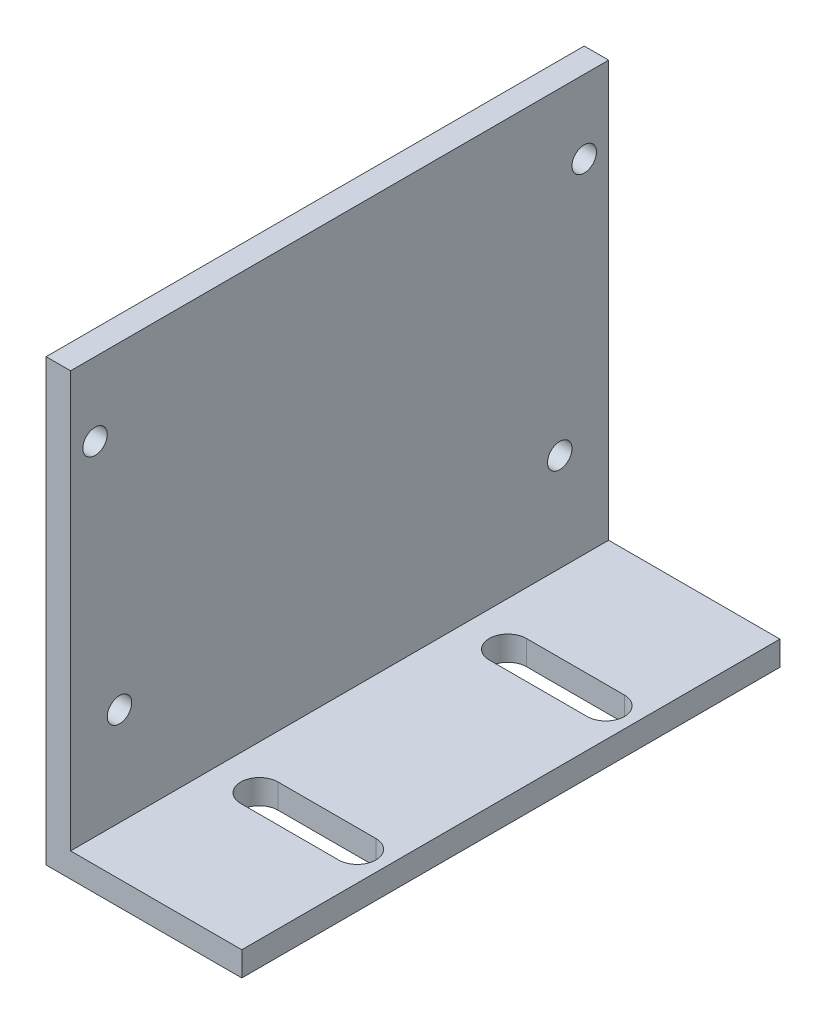
SolidWorks part; units mm, degrees
ref_plane "Front Plane" through (0, 0, 0) normal (0, 0, 1) x (1, 0, 0)
ref_plane "Top Plane" through (0, 0, 0) normal (0, 1, 0) x (1, 0, 0)
ref_plane "Right Plane" through (0, 0, 0) normal (1, 0, 0) x (0, 0, -1)
sketch "Sketch1" plane through (0, 0, 0) normal (0, 0, 1) x (1, 0, 0)
  line L0 (0, 0) -> (-20, 0)
  line L1 (-20, 0) -> (-20, 45)
  line L2 (-20, 45) -> (-17.5, 45)
  line L3 (-17.5, 45) -> (-17.5, 2.5)
  line L4 (-17.5, 2.5) -> (0, 2.5)
  line L5 (0, 2.5) -> (0, 0)
  point P7 (0, -0.2069)
  dimension "D1" = 45
  dimension "D2" = 20
  dimension "D3" = 2.5
  dimension "D4" = 2.5
extrude "Boss-Extrude1" add sketch "Sketch1" along normal mid plane 55
sketch "Sketch2" plane through (-17.5, 0, 0) normal (1, 0, 0) x (0, 0, -1)
  line L0 (25, 37.5) -> (27.5, 37.5) construction
  line L1 (-25, 37.5) -> (-27.5, 37.5) construction
  line L2 (-27.5, 45) -> (-27.5, 0) construction
  line L3 (27.5, 45) -> (27.5, 0) construction
  line L4 (-22.5, 12.5) -> (-27.5, 12.5) construction
  line L5 (22.5, 12.5) -> (27.5, 12.5) construction
  line L7 (-27.5, 0) -> (27.5, 0) construction
  circle A0 centre (-25, 37.5) radius 1.25
  circle A1 centre (25, 37.5) radius 1.25
  circle A2 centre (-22.5, 12.5) radius 1.25
  circle A3 centre (22.5, 12.5) radius 1.25
  point P8 (0, 0)
  point P16 (0, 0)
  dimension "D1" = 2.5
  dimension "D2" = 50
  dimension "D3" = 45
  dimension "D4" = 25
  dimension "D5" = 12.5
extrude "Cut-Extrude1" cut sketch "Sketch2" against normal up to next
sketch "Sketch3" plane through (0, 2.5, 0) normal (0, 1, 0) x (1, 0, 0)
  line L0 (-13, -12.7) -> (-3, -12.7) construction
  line L1 (-13, -10.795) -> (-3, -10.795)
  line L2 (-13, -14.605) -> (-3, -14.605)
  line L3 (-22.4407, 0) -> (10.5779, 0) construction
  line L4 (-13, 12.7) -> (-3, 12.7) construction
  line L5 (-13, 10.795) -> (-3, 10.795)
  line L6 (-13, 14.605) -> (-3, 14.605)
  arc A0 (-13, -10.795) -> (-13, -14.605) centre (-13, -12.7) ccw
  arc A1 (-3, -14.605) -> (-3, -10.795) centre (-3, -12.7) ccw
  arc A2 (-13, 10.795) -> (-13, 14.605) centre (-13, 12.7) cw
  arc A3 (-3, 14.605) -> (-3, 10.795) centre (-3, 12.7) cw
  point P2 (-8, -12.7)
  point P12 (-8, 12.7)
  dimension "D1" = 1.905
  dimension "D3" = 3
  dimension "D2" = 10
  dimension "D4" = 14.605
extrude "Cut-Extrude2" cut sketch "Sketch3" against normal up to next
